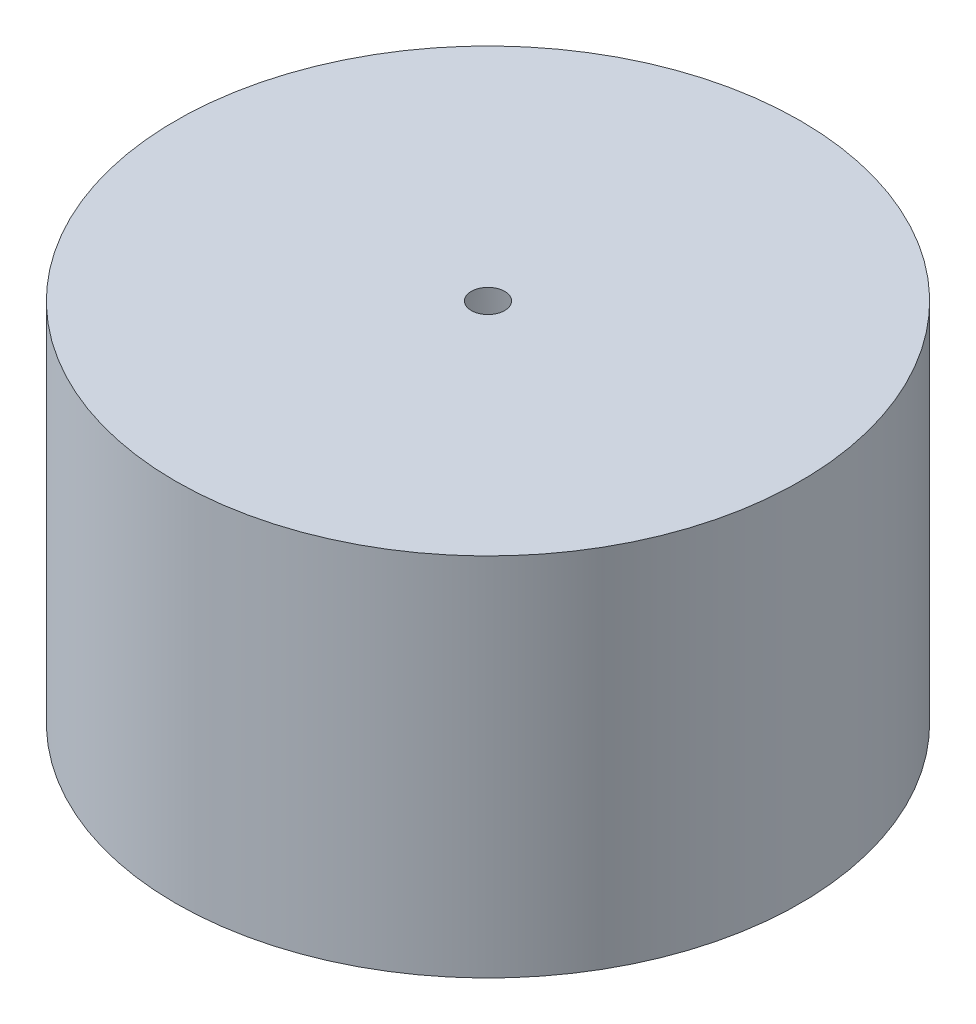
SolidWorks part; units mm, degrees
ref_plane "Спереди" through (0, 0, 0) normal (0, 0, 1) x (1, 0, 0)
ref_plane "Сверху" through (0, 0, 0) normal (0, 1, 0) x (1, 0, 0)
ref_plane "Справа" through (0, 0, 0) normal (1, 0, 0) x (0, 0, -1)
sketch "Эскиз1" plane through (0, 0, 0) normal (0, 0, 1) x (1, 0, 0)
  line L0 (0, 0) -> (0, 64.3029) construction
  line L33 (30, 28.7946) -> (30, 26.2946)
  line L34 (30, 26.2946) -> (28.4, 26.2946)
  line L35 (28.4, 26.2946) -> (28.4, 18.2946)
  line L37 (8, 58.6338) -> (2, 62.0979)
  line L38 (2, 62.0979) -> (37.4277, 62.0979)
  line L40 (28.4, 18.2946) -> (37.4277, 18.2946)
  line L41 (37.4277, 18.2946) -> (37.4277, 62.0979)
  line L42 (8, 58.6338) -> (8.3476, 52.0019)
  line L43 (8.3476, 52.0019) -> (10.7476, 49.4019)
  line L44 (8, 58.6338) -> (8, 51.4355) construction
  line L45 (10.7476, 49.4019) -> (10.9672, 43.1119)
  line L46 (10.7476, 49.4019) -> (10.7476, 37.0019) construction
  line L50 (12.2182, 33.9946) -> (19.2771, 33.9946) construction
  line L51 (12.2182, 33.9946) -> (16.6302, 29.9946)
  line L53 (30, 28.7946) -> (30, 29.9946)
  line L54 (16.6302, 29.9946) -> (30, 29.9946)
  line L55 (11.9976, 38.5019) -> (11.9976, 41.6565) construction
  line L56 (11.9976, 40.3132) -> (12.2182, 33.9946)
  arc A0 (11.9976, 40.3132) -> (10.9672, 43.1119) centre (11.33, 41.6565) ccw
  point P8 (10.9083, 44.8)
  point P11 (11.33, 41.6565)
  point P15 (0, 61.8065)
  point P17 (11.9976, 38.5019)
  point P19 (12.2182, 33.931)
  dimension "D5" = 16
  dimension "D14" = 3
  dimension "D3" = 2.6
  dimension "D4" = 3
  dimension "D6" = 60
  dimension "D8" = 4
  dimension "D9" = 2
  dimension "D10" = 2.4
  dimension "D12" = 20.15
  dimension "D13" = 11.33
  dimension "D15" = 1.25
  dimension "D16" = 10.9
  dimension "D17" = 4
  dimension "D18" = 2
  dimension "D20" = 2.5
  dimension "D21" = 8
  dimension "D23" = 1.6
  dimension "D26" = 6.29
revolve "Повернуть1" add sketch "Эскиз1" angle 360 about L0 reverse direction yes
